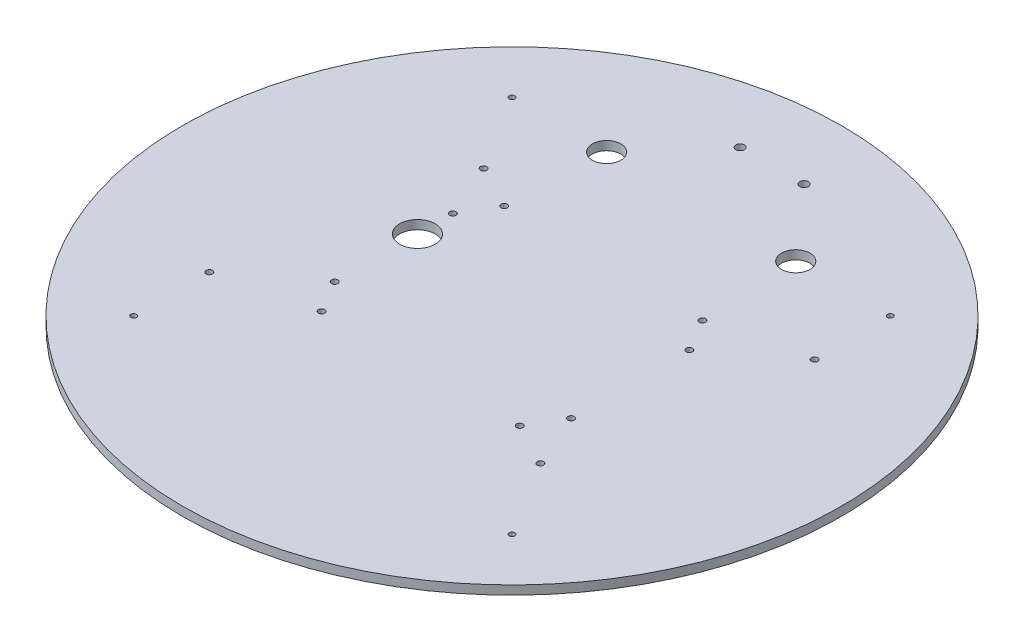
SolidWorks part; units mm, degrees
ref_plane "Front Plane" through (0, 0, 0) normal (0, 0, 1) x (1, 0, 0)
ref_plane "Top Plane" through (0, 0, 0) normal (0, 1, 0) x (1, 0, 0)
ref_plane "Right Plane" through (0, 0, 0) normal (1, 0, 0) x (0, 0, -1)
sketch "Sketch1" plane through (0, 0, 0) normal (0, 1, 0) x (1, 0, 0)
  circle A0 centre (0, 0) radius 177
  circle A1 centre (-101.6, -101.6) radius 1.5
  circle A2 centre (-101.6, 101.6) radius 1.5
  circle A3 centre (101.6, 101.6) radius 1.5
  circle A4 centre (101.6, -101.6) radius 1.5
  point P11 (0, 0)
  point P12 (0, 0)
  point P13 (0, 0)
  point P14 (0, 0)
  point P15 (0, 0)
  point P16 (0, 0)
  point P17 (0, 0)
  point P18 (0, 0)
  point P19 (0, 0)
  point P20 (0, 0)
  point P21 (0, 0)
  point P22 (0, 0)
  point P23 (0, 0)
  point P24 (0, 0)
  point P25 (0, 0)
  point P26 (0, 0)
  dimension "D1" = 354
  dimension "D2" = 3
  dimension "D3" = 3
  dimension "D4" = 3
  dimension "D5" = 3
  dimension "D8" = 203.2
  dimension "D6" = 203.2
  dimension "D7" = 203.2
  dimension "D9" = 203.2
  dimension "D10" = 0
  dimension "D11" = 101.6
  dimension "D12" = 101.6
extrude "Boss-Extrude1" add sketch "Sketch1" along normal blind 4.7625
sketch "Sketch2" plane through (0, 4.7625, 0) normal (0, 1, 0) x (1, 0, 0)
  circle A0 centre (-53.213, 49.022) radius 1.7
  circle A1 centre (53.213, 49.022) radius 1.7
  circle A3 centre (-53.213, -49.022) radius 1.7
  circle A4 centre (53.213, -49.022) radius 1.7
  dimension "D1" = 3.4
  dimension "D2" = 3.4
  dimension "D3" = 3.4
  dimension "D4" = 3.4
  dimension "D6" = 0
  dimension "D7" = 0
  dimension "D8" = 106.426
  dimension "D12" = 53.213
  dimension "D5" = 106.426
  dimension "D9" = 0
  dimension "D10" = 98.044
  dimension "D11" = 49.022
extrude "JetsonHoles" cut sketch "Sketch2" against normal through all
sketch "Sketch3" plane through (0, 4.7625, 0) normal (0, 1, 0) x (1, 0, 0)
  circle A0 centre (-63.5, 12.7) radius 9.525
  dimension "D1" = 19.05
  dimension "D3" = 12.7
  dimension "D2" = 63.5
extrude "UART-Wire-Hole" cut sketch "Sketch3" against normal through all
sketch "Sketch4" plane through (0, 4.7625, 0) normal (0, 1, 0) x (1, 0, 0)
  circle A0 centre (-17.145, 139.7) radius 2.286
  circle A1 centre (17.145, 139.7) radius 2.286
  dimension "D1" = 4.572
  dimension "D2" = 4.572
  dimension "D6" = 139.7
  dimension "D3" = 0
  dimension "D4" = 34.29
  dimension "D5" = 17.145
extrude "Camera-Hole" cut sketch "Sketch4" against normal through all
sketch "Sketch5" plane through (0, 4.7625, 0) normal (0, 1, 0) x (1, 0, 0)
  circle A0 centre (-63.5, -31.75) radius 1.7
  circle A1 centre (63.5, -31.75) radius 1.7
  circle A2 centre (63.5, 31.75) radius 1.7
  circle A3 centre (-63.5, 31.75) radius 1.7
  point P4 (73.2036, -37.9463)
  point P7 (70.2099, 45.545)
  point P10 (-72.4903, 50.8671)
  point P11 (70.2099, -48.7796)
  point P12 (94.8849, 37.6107)
  dimension "D1" = 3.4
  dimension "D2" = 3.4
  dimension "D3" = 3.4
  dimension "D4" = 3.4
  dimension "D7" = 0
  dimension "D9" = 127
  dimension "D5" = 0
  dimension "D6" = 0
  dimension "D8" = 0
  dimension "D10" = 63.5
  dimension "D11" = 63.5
  dimension "D12" = 31.75
extrude "StandoffHoles" cut sketch "Sketch5" against normal through all
sketch "Sketch6" plane through (0, 4.7625, 0) normal (0, 1, 0) x (1, 0, 0)
  circle A0 centre (101.6, 60.96) radius 1.7
  circle A1 centre (76.2, -60.96) radius 1.7
  circle A2 centre (63.5, -31.75) radius 1.7 construction
  circle A3 centre (-101.6, -60.96) radius 1.7
  circle A4 centre (-76.2, 60.96) radius 1.7
  circle A6 centre (-63.5, 31.75) radius 1.7 construction
  circle A7 centre (-50.8, 101.6) radius 7.62
  circle A8 centre (50.8, 101.6) radius 7.62
  point P17 (37.114, 85.8554)
  point P18 (37.114, 85.8554)
  point P19 (0, 0)
  dimension "D1" = 3.4
  dimension "D2" = 3.4
  dimension "D4" = 121.92
  dimension "D7" = 3.4
  dimension "D8" = 3.4
  dimension "D12" = 12.7
  dimension "D13" = 15.24
  dimension "D14" = 15.24
  dimension "D15" = 101.6
  dimension "D16" = 0
  dimension "D17" = 50.8
  dimension "D18" = 50.8
  dimension "D3" = 25.4
  dimension "D5" = 60.96
  dimension "D6" = 12.7
  dimension "D9" = 25.4
  dimension "D10" = 121.92
  dimension "D11" = 60.96
extrude "NiMH_Holes" cut sketch "Sketch6" against normal through all
